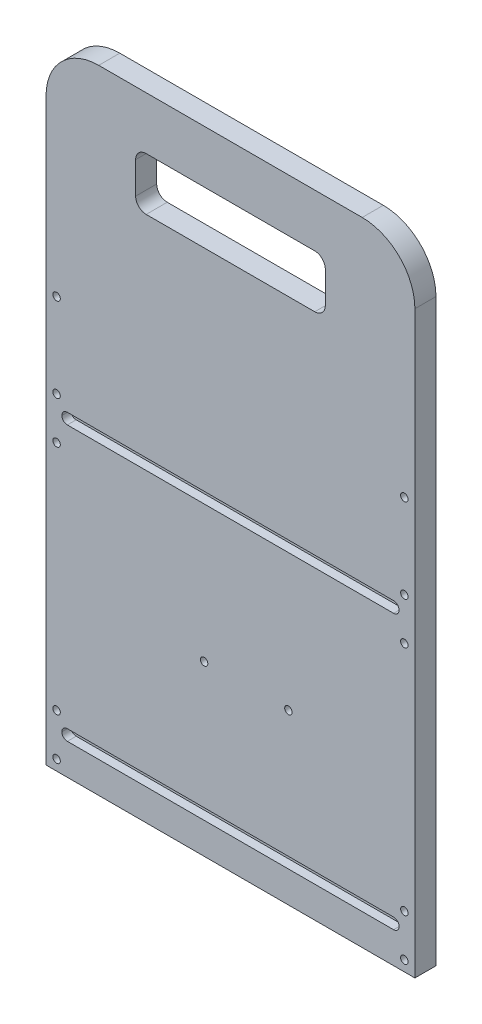
SolidWorks part; units mm, degrees
material "Delrin 2700 NC010, Low Viscosity Acetal Copolymer (SS)"
ref_plane "Front Plane" through (0, 0, 0) normal (0, 0, 1) x (1, 0, 0)
ref_plane "Top Plane" through (0, 0, 0) normal (0, 1, 0) x (1, 0, 0)
ref_plane "Right Plane" through (0, 0, 0) normal (1, 0, 0) x (0, 0, -1)
sketch "Sketch1" plane through (0, 0, 0) normal (0, 0, 1) x (1, 0, 0)
  line L1 (-111.125, -190.5) -> (111.125, -190.5)
  line L2 (-111.125, -190.5) -> (-111.125, 190.5)
  line L3 (-111.125, 190.5) -> (111.125, 190.5)
  line L4 (111.125, -190.5) -> (111.125, 190.5)
  line L5 (-111.125, -190.5) -> (111.125, 190.5) construction
  line L6 (-111.125, 190.5) -> (111.125, -190.5) construction
  point P0 (0, 0)
  dimension "D1" = 222.25
  dimension "D2" = 381
extrude "Boss-Extrude1" add sketch "Sketch1" along normal blind 12.7 contours L3 L4 L1 L2
fillet "Fillet1" radius 31.75 2 edges at (-111.125, 190.5, 6.35) (111.125, 190.5, 6.35)
sketch "Sketch2" plane through (0, 0, 12.7) normal (0, 0, 1) x (1, 0, 0)
  line L0 (-79.375, 190.5) -> (79.375, 190.5) construction
  line L1 (-57.15, 158.75) -> (57.15, 158.75)
  line L2 (-57.15, 158.75) -> (-57.15, 127)
  line L3 (-57.15, 127) -> (57.15, 127)
  line L4 (57.15, 158.75) -> (57.15, 127)
  point P4 (0, 127)
  dimension "D1" = 114.3
  dimension "D2" = 31.75
  dimension "D3" = 31.75
extrude "Cut-Extrude1" cut sketch "Sketch2" against normal up to surface (12.7 mm away) up to face at (0, 55.1085, 0)
fillet "Fillet2" radius 6.35 4 edges at (57.15, 127, 6.35) (57.15, 158.75, 6.35) (-57.15, 158.75, 6.35) (-57.15, 127, 6.35)
sketch "Sketch3" plane through (0, 0, 12.7) normal (0, 0, 1) x (1, 0, 0)
  line L0 (-111.125, -190.5) -> (111.125, -190.5) construction
  line L1 (-101.6, -171.704) -> (101.6, -171.704)
  line L2 (-101.6, -171.704) -> (-101.6, -165.1)
  line L3 (-101.6, -165.1) -> (101.6, -165.1)
  line L4 (101.6, -171.704) -> (101.6, -165.1)
  line L6 (-101.6, -6.604) -> (101.6, -6.604)
  line L7 (-101.6, -6.604) -> (-101.6, 0)
  line L8 (-101.6, 0) -> (101.6, 0)
  line L9 (101.6, -6.604) -> (101.6, 0)
  point P4 (0, -165.1)
  point P12 (0, -6.604)
  dimension "D1" = 18.796
  dimension "D2" = 6.604
  dimension "D3" = 203.2
  dimension "D4" = 203.2
  dimension "D5" = 6.604
  dimension "D6" = 183.896
extrude "Cut-Extrude2" cut sketch "Sketch3" against normal blind 5.334
fillet "Fillet3" radius 3.302 8 edges at (101.6, -165.1, 10.033) (101.6, -171.704, 10.033) (-101.6, -171.704, 10.033) (-101.6, -165.1, 10.033) (101.6, -6.604, 10.033) (101.6, 0, 10.033) (-101.6, 0, 10.033) (-101.6, -6.604, 10.033)
hole_wizard "CSK for #8 Flat Head Machine Screw (100)1" positions "Sketch6" profile "Sketch8" countersink size "#8" standard "ANSI Inch" end condition through all
sketch "Sketch6" plane through (0, 0, 0) normal (0, 0, -1) x (-1, 0, 0)
  line L0 (111.125, -190.5) -> (-111.125, -190.5) construction
  line L1 (-111.125, -190.5) -> (-111.125, 158.75) construction
  line L2 (111.125, -190.5) -> (111.125, 158.75) construction
  point P0 (-104.775, -184.15)
  point P2 (-104.775, -158.75)
  point P4 (104.775, -158.75)
  point P6 (104.775, -184.15)
  point P20 (-104.775, -19.05)
  point P22 (-104.775, 6.35)
  point P24 (104.775, 6.35)
  point P26 (104.775, -19.05)
  point P35 (-104.775, 57.15)
  point P37 (104.775, 57.15)
  point P43 (-34.925, -88.9)
  point P45 (15.875, -88.9)
  dimension "D1" = 6.35
  dimension "D2" = 6.35
  dimension "D3" = 6.35
  dimension "D4" = 25.4
  dimension "D5" = 171.45
  dimension "D6" = 25.4
  dimension "D7" = 50.8
  dimension "D8" = 50.8
  dimension "D9" = 76.2
  dimension "D10" = 101.6
sketch "Sketch8" plane through (104.775, -184.15, 0) normal (1, 0, 0) x (0, 1, 0)
  line L0 (0, 0) -> (0, 12.7)
  line L1 (0, 12.7) -> (2.2479, 12.7)
  line L2 (2.2479, 12.7) -> (2.2479, 1.6518)
  line L3 (2.2479, 1.6518) -> (4.2164, 0)
  line L5 (4.2164, 0) -> (0, 0)
  line L6 (-2.2479, 1.6518) -> (-4.2164, 0) construction
  line L11 (0, -6.35) -> (0, 107.95) construction
  dimension "Thru Hole Dia." = 4.4958
  dimension "Thru Hole Depth" = 12.7
  dimension "Near C'Sink Dia." = 8.4328
  dimension "Near C'Sink Angle" = 100
equation "\"D4@Sketch3\"=\"D3@Sketch3\""
equation "\"D5@Sketch3\"=\"D2@Sketch3\""
equation "\"D3@Sketch6\"=\"D2@Sketch6\""
equation "\"D6@Sketch6\"=\"D4@Sketch6\""
